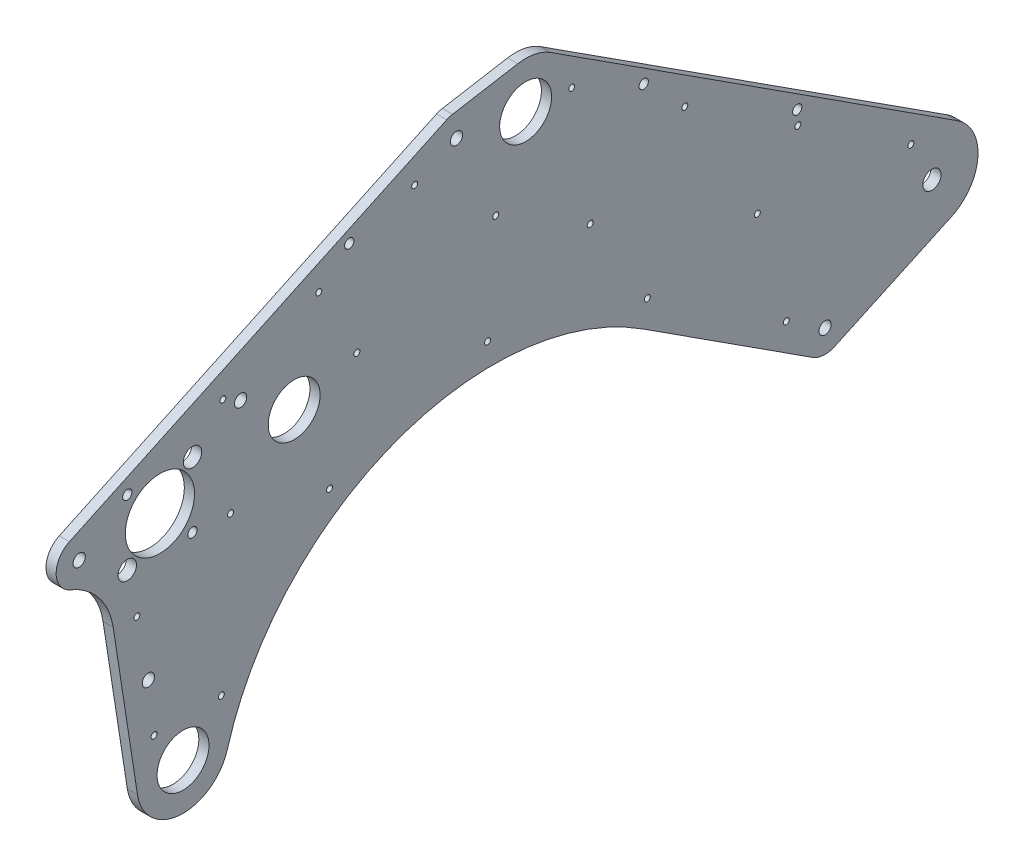
SolidWorks part; units mm, degrees
material "Acrylic (Medium-high impact)"
ref_plane "Front" through (0, 0, 0) normal (0, 0, 1) x (1, 0, 0)
ref_plane "Top" through (0, 0, 0) normal (0, 1, 0) x (1, 0, 0)
ref_plane "Right" through (0, 0, 0) normal (1, 0, 0) x (0, 0, -1)
sketch "Sketch1" plane through (0, 0, 0) normal (1, 0, 0) x (0, 0, -1)
  line L0 (-109.5375, -69.85) -> (-109.5375, -196.85)
  line L1 (-109.5375, -196.85) -> (-160.3375, -196.85)
  line L2 (-192.0875, -165.1) -> (-192.0875, -101.6)
  line L3 (-160.3375, -69.85) -> (-109.5375, -69.85)
  line L4 (-28.6872, -260.35) -> (-968.3377, -260.35) construction
  line L5 (-414.3375, -165.1) -> (-414.3375, -101.6) construction
  line L6 (-101.6, -57.15) -> (-76.2, -57.15)
  line L7 (-101.6, -57.15) -> (-101.6, -82.55)
  line L8 (-101.6, -82.55) -> (-76.2, -82.55)
  line L9 (-76.2, -57.15) -> (-76.2, -82.55)
  line L10 (-160.3375, 152.4) -> (-109.5375, 152.4) construction
  line L11 (-412.4442, -70.6452) -> (-160.3375, -101.6) construction
  line L12 (-351.247, 65.9398) -> (-160.3375, -101.6) construction
  line L13 (-223.7678, 144.3524) -> (-160.3375, -101.6) construction
  line L14 (-430.6959, -62.4675) -> (-369.4987, 74.1175)
  line L15 (-332.9953, 57.762) -> (-394.1925, -78.8229)
  line L16 (-361.7254, 82.9751) -> (-234.2463, 161.3877)
  line L17 (-109.5375, -69.85) -> (-109.5375, 357.098) construction
  line L18 (-213.2894, 127.3171) -> (-340.7685, 48.9045)
  line L19 (-515.9375, 289.2974) -> (-515.9375, -104.2984) construction
  line L20 (-405.2884, 55.4141) -> (-392.5489, -68.6015)
  line L21 (-432.3395, -72.6889) -> (-445.079, 51.3266)
  circle A0 centre (0, 0) radius 5.0419
  circle A1 centre (-412.4442, -70.6452) radius 11.557
  circle A2 centre (-351.247, 65.9398) radius 11.557
  circle A3 centre (-223.7678, 144.3524) radius 11.557
  arc A4 (-160.3375, -196.85) -> (-192.0875, -165.1) centre (-160.3375, -165.1) cw
  arc A5 (-192.0875, -101.6) -> (-160.3375, -69.85) centre (-160.3375, -101.6) cw
  circle A6 centre (-328.0084, -139.9571) radius 120.65
  arc A7 (-414.3375, -101.6) -> (-160.3375, 152.4) centre (-160.3375, -101.6) cw construction
  circle A12 centre (-425.1837, 53.3704) radius 31.75
  arc A15 (-394.1925, -78.8229) -> (-430.6959, -62.4675) centre (-412.4442, -70.6452) cw
  arc A16 (-369.4987, 74.1175) -> (-332.9953, 57.762) centre (-351.247, 65.9398) cw
  arc A17 (-340.7685, 48.9045) -> (-361.7254, 82.9751) centre (-351.247, 65.9398) cw
  arc A18 (-234.2463, 161.3877) -> (-213.2894, 127.3171) centre (-223.7678, 144.3524) cw
  arc A19 (-445.079, 51.3266) -> (-405.2884, 55.4141) centre (-425.1837, 53.3704) cw
  arc A20 (-392.5489, -68.6015) -> (-432.3395, -72.6889) centre (-412.4442, -70.6452) cw
  point P45 (0, 0)
  point P46 (0, 0)
  point P51 (-328.0084, -139.9571)
  point P56 (0, 0)
  point P58 (0, 0)
  point P59 (0, 0)
  circle B0 centre (-223.7678, 144.3524) radius 20
  circle B1 centre (-351.247, 65.9398) radius 20
  circle B2 centre (-412.4442, -70.6452) radius 20
  circle B3 centre (-425.1837, 53.3704) radius 20
  dimension "D1" = 10.0838
  dimension "D2" = 23.114
  dimension "D4" = 31.75
  dimension "D10" = 241.3
  dimension "D19" = 63.5
  dimension "D26" = 70.6452
  dimension "D27" = 412.4442
  dimension "D3" = 127
  dimension "D5" = 82.55
  dimension "D6" = 190.5
  dimension "D7" = 25.4
  dimension "D8" = 7.9375
  dimension "D9" = 203.2
  dimension "D12" = 101.6
  dimension "D13" = 57.15
  dimension "D14" = 34.27
  dimension "D15" = 34.269
  dimension "D16" = 7
  dimension "D24" = 406.4
  dimension "D21" = 30
  dimension "D11" = 222.25
sketch_block_instance "Block1-1"
sketch_block "Block1" parameters "D1"=40
sketch_block_instance "Block2-1"
sketch_block "Block2"
sketch_block_instance "Block3-1"
sketch_block "Block3"
sketch_block_instance "Block4-1"
sketch_block "Block4" parameters "D1"=40
other "Belt1"
other "Belt2"
other "Belt4"
sketch "Sketch3" plane through (0, 0, 0) normal (1, 0, 0) x (0, 0, -1)
  line L0 (-412.4442, -70.6452) -> (0, 0) construction
  line L1 (0, 0) -> (-58.8496, -41.2069) construction
  line L2 (0, 0) -> (-70.6452, 412.4442) construction
  line L3 (0, 0) -> (-41.2069, 58.8496) construction
  line L4 (-58.8496, -41.2069) -> (-64.0291, -10.9672) construction
  line L5 (-41.2069, 58.8496) -> (-10.9672, 64.0291) construction
  line L6 (-41.2069, 58.8496) -> (-58.8496, -41.2069)
  line L7 (-4.2676, 268.3428) -> (-41.2069, 58.8496)
  line L8 (0, 0) -> (144.3524, 223.7678) construction
  line L9 (0, 0) -> (-223.7678, 144.3524) construction
  line L10 (-223.7678, 144.3524) -> (-193.3694, -33.1211) construction
  line L11 (144.3524, 223.7678) -> (-33.1211, 193.3694) construction
  circle A0 centre (-70.6452, 412.4442) radius 25.4
  dimension "D1" = 50.8
  dimension "D2" = 90
  dimension "D3" = 101.6
  dimension "D4" = 212.725
  dimension "D5" = 80
sketch "Sketch2" plane through (0, 0, 0) normal (1, 0, 0) x (0, 0, -1)
  line L0 (-437.5463, -74.5243) -> (-450.9257, 12.0539)
  line L1 (-475.0213, 64.8709) -> (-267.2555, 162.203)
  line L2 (-412.4442, -70.6452) -> (-412.4442, 0) construction
  line L4 (13.7691, 21.3441) -> (-209.9987, 165.6966)
  line L7 (-65.7341, -51.879) -> (-158.9605, 8.2613)
  line L10 (-53.5189, -52.734) -> (10.6613, -23.0542)
  line L11 (-264.015, 163.2196) -> (-228.0621, 169.3868)
  line L13 (-443.1442, 35.4098) -> (-407.2231, 71.3309) construction
  line L14 (-443.1442, 71.3309) -> (-407.2231, 35.4098) construction
  circle A0 centre (-223.7678, 144.3524) radius 14.2875
  circle A1 centre (-351.247, 65.9398) radius 14.2875
  circle A2 centre (-412.4442, -70.6452) radius 14.2875
  circle A3 centre (-425.1837, 53.3704) radius 19.05
  circle A9 centre (0, 0) radius 5.0419 construction
  circle A10 centre (0, 0) radius 5.0419
  arc A13 (-437.5463, -74.5243) -> (-388.0343, -77.6678) centre (-412.4442, -70.6452) ccw
  arc A16 (10.6613, -23.0542) -> (13.7691, 21.3441) centre (0, 0) ccw
  arc A18 (-158.9605, 8.2613) -> (-388.0343, -77.6678) centre (-241.575, -119.8036) ccw
  circle A19 centre (-58.8496, -41.2069) radius 3.3782
  circle A22 centre (-261.8678, 150.7024) radius 3.3782
  arc A23 (-267.2555, 162.203) -> (-264.015, 163.2196) centre (-261.8678, 150.7024) cw
  circle A24 centre (-223.7678, 144.3524) radius 25.4 construction
  circle A27 centre (-407.2231, 71.3309) radius 5.08
  circle A28 centre (-443.1442, 71.3309) radius 2.5527
  circle A29 centre (-443.1442, 35.4098) radius 5.08
  circle A30 centre (-407.2231, 35.4098) radius 2.5527
  circle A31 centre (-425.1837, 53.3704) radius 25.4 construction
  circle A32 centre (-469.6337, 53.3704) radius 3.3782
  arc A34 (-475.0213, 64.8709) -> (-474.3699, 41.5866) centre (-469.6337, 53.3704) ccw
  arc A35 (-474.3699, 41.5866) -> (-450.9257, 12.0539) centre (-488.5787, 6.2352) cw
  circle A37 centre (-425.1837, 53.3704) radius 31.75 construction
  circle A38 centre (-469.6337, 53.3704) radius 7.9375 construction
  circle A39 centre (-431.5337, -22.8296) radius 3.3782
  circle A40 centre (-431.5337, -22.8296) radius 7.9375 construction
  circle A41 centre (-380.7337, 85.1204) radius 3.3782
  arc A42 (-65.7341, -51.879) -> (-53.5189, -52.734) centre (-58.8496, -41.2069) ccw
  arc A43 (-228.0621, 169.3868) -> (-209.9987, 165.6966) centre (-223.7678, 144.3524) cw
  circle A44 centre (-351.247, 65.9398) radius 11.557 construction
  point P11 (0, 0)
  point P14 (-353.2365, 70.2706)
  point P45 (0, 0)
  dimension "D1" = 28.575
  dimension "D2" = 38.1
  dimension "D3" = 6.35
  dimension "D4" = 50.8
  dimension "D5" = 12.7
  dimension "D6" = 38.1
  dimension "D7" = 25.4
  dimension "D8" = 152.4
  dimension "D10" = 6.7564
  dimension "D11" = 6.7564
  dimension "D12" = 15.875
  dimension "D13" = 12.7
  dimension "D17" = 15.875
  dimension "D18" = 5.1054
  dimension "D19" = 10.16
  dimension "D20" = 50.8
  dimension "D21" = 25.4
  dimension "D22" = 38.1
  dimension "D23" = 6.35
  dimension "D16" = 44.45
  dimension "D15" = 31.75
  dimension "D24" = 76.2
  dimension "D25" = 44.45
  dimension "D9" = 12.7
extrude "Boss-Extrude1" add sketch "Sketch2" along normal blind 5.588
sketch "Sketch4" plane through (5.588, 0, 0) normal (1, 0, 0) x (0, 0, -1)
  line L0 (-351.247, 65.9398) -> (-223.7678, 144.3524) construction
  line L1 (-267.2555, 162.203) -> (-475.0213, 64.8709) construction
  line L3 (-320.8714, 130.0733) -> (-435.8771, 76.1966) construction
  line L4 (-435.8771, 76.1966) -> (-425.1837, 53.3704) construction
  line L6 (13.7691, 21.3441) -> (-209.9987, 165.6966) construction
  line L11 (-243.2375, 179.5822) -> (-158.7161, 125.0575) construction
  line L12 (-158.7161, 125.0575) -> (-74.1946, 70.5328) construction
  line L13 (-74.1946, 70.5328) -> (10.3268, 16.0081) construction
  line L14 (-243.2375, 179.5822) -> (-261.8678, 150.7024) construction
  line L15 (0, 0) -> (10.3268, 16.0081) construction
  circle A4 centre (-320.8714, 130.0733) radius 2.5527
  circle A5 centre (-158.7161, 125.0575) radius 2.5527
  circle A6 centre (-74.1946, 70.5328) radius 2.5527
  dimension "D1" = 6.35
  dimension "D2" = 5.1054
  dimension "D3" = 127
  dimension "D6" = 6.35
extrude "Cut-Extrude1" cut sketch "Sketch4" against normal through all
sketch "Sketch6" plane through (5.588, 0, 0) normal (1, 0, 0) x (0, 0, -1)
  line L0 (-11.6, 22.5964) -> (-73.856, 62.7577) construction
  line L1 (-390.495, 90.4444) -> (-337.682, 115.1858) construction
  line L2 (-337.682, 115.1858) -> (-284.869, 139.9271) construction
  line L3 (-391.3598, -50.3591) -> (-331.7679, 18.4833) construction
  line L4 (-58.8496, -41.2069) -> (-152.0759, 18.9333)
  line L5 (-58.8496, -41.2069) -> (-152.0759, 18.9333) construction
  line L6 (-331.7679, 18.4833) -> (-244.7441, 45.266) construction
  line L7 (-244.7441, 45.266) -> (-156.7564, 21.8432) construction
  line L8 (-156.7564, 21.8432) -> (-80.1937, -27.4378) construction
  line L9 (-73.856, 62.7577) -> (-136.1119, 102.9189) construction
  line L10 (-267.2555, 162.203) -> (-475.0213, 64.8709) construction
  line L11 (13.7691, 21.3441) -> (-209.9987, 165.6966) construction
  line L12 (-136.1119, 102.9189) -> (-198.3678, 143.0802) construction
  line L13 (-437.8454, 10.5687) -> (-428.3547, -50.8458) construction
  line L14 (-450.9257, 12.0539) -> (-437.5463, -74.5243) construction
  line L15 (-240.2156, 103.0201) -> (-316.6918, 75.7974) construction
  line L16 (-316.6918, 75.7974) -> (-386.2566, 33.9594) construction
  line L17 (-284.869, 139.9271) -> (-240.2156, 103.0201) construction
  line L18 (-240.2156, 103.0201) -> (-198.3678, 143.0802) construction
  line L19 (-240.2156, 103.0201) -> (-244.7441, 45.266) construction
  line L20 (-437.8454, 10.5687) -> (-386.2566, 33.9594) construction
  line L21 (-386.2566, 33.9594) -> (-390.495, 90.4444) construction
  line L22 (-386.2566, 33.9594) -> (-331.7679, 18.4833) construction
  line L23 (-335.6008, 116.1607) -> (-297.7827, 35.434) construction
  line L24 (-156.7564, 21.8432) -> (-188.1929, 73.0142) construction
  line L25 (-188.1929, 73.0142) -> (-136.1119, 102.9189) construction
  line L26 (-240.2156, 103.0201) -> (-188.1929, 73.0142) construction
  line L27 (-73.856, 62.7577) -> (-96.1612, 31.8694) construction
  line L28 (-96.1612, 31.8694) -> (-80.1937, -27.4378) construction
  line L29 (-96.1612, 31.8694) -> (-156.7564, 21.8432) construction
  circle A0 centre (-11.6, 22.5964) radius 1.651
  circle A1 centre (-156.7564, 21.8432) radius 1.651
  circle A2 centre (-73.856, 62.7577) radius 1.651
  circle A3 centre (-244.7441, 45.266) radius 1.651
  circle A4 centre (-284.869, 139.9271) radius 1.651
  circle A5 centre (-331.7679, 18.4833) radius 1.651
  circle A6 centre (-391.3598, -50.3591) radius 1.651
  circle A7 centre (-437.8454, 10.5687) radius 1.651
  circle A8 centre (-337.682, 115.1858) radius 1.651
  circle A9 centre (-390.495, 90.4444) radius 1.651
  circle A10 centre (-136.1119, 102.9189) radius 1.651
  circle A11 centre (-80.1937, -27.4378) radius 1.651
  circle A12 centre (-261.8678, 150.7024) radius 3.3782 construction
  circle A13 centre (-407.2231, 71.3309) radius 5.08 construction
  arc A14 (-152.0759, 18.9333) -> (-400.2393, -74.1565) centre (-241.575, -119.8036) ccw
  arc A15 (-152.0759, 18.9333) -> (-400.2393, -74.1565) centre (-241.575, -119.8036) ccw construction
  circle A16 centre (0, 0) radius 5.0419 construction
  circle A17 centre (-428.3547, -50.8458) radius 1.651
  circle A18 centre (-198.3678, 143.0802) radius 1.651
  circle A19 centre (-223.7678, 144.3524) radius 14.2875 construction
  circle A20 centre (-412.4442, -70.6452) radius 14.2875 construction
  circle A21 centre (-443.1442, 35.4098) radius 5.08 construction
  circle A22 centre (-240.2156, 103.0201) radius 1.651
  circle A23 centre (-386.2566, 33.9594) radius 1.651
  circle A24 centre (-316.6918, 75.7974) radius 1.651
  circle A25 centre (-188.1929, 73.0142) radius 1.651
  circle A26 centre (-96.1612, 31.8694) radius 1.651
  point P62 (-95.2521, 35.434)
  dimension "D1" = 3.302
  dimension "D2" = 12.7
  dimension "D5" = 12.7
  dimension "D7" = 25.4
  dimension "D3" = 25.4
  dimension "D4" = 25.4
  dimension "D6" = 25.4
  dimension "D8" = 12.7
  dimension "D9" = 25.4
  dimension "D10" = 25.4
  dimension "D11" = 12.7
  dimension "D12" = 25.4
  dimension "D13" = 25.4
  dimension "D14" = 38.1
extrude "Cut-Extrude2" cut sketch "Sketch6" against normal through all
